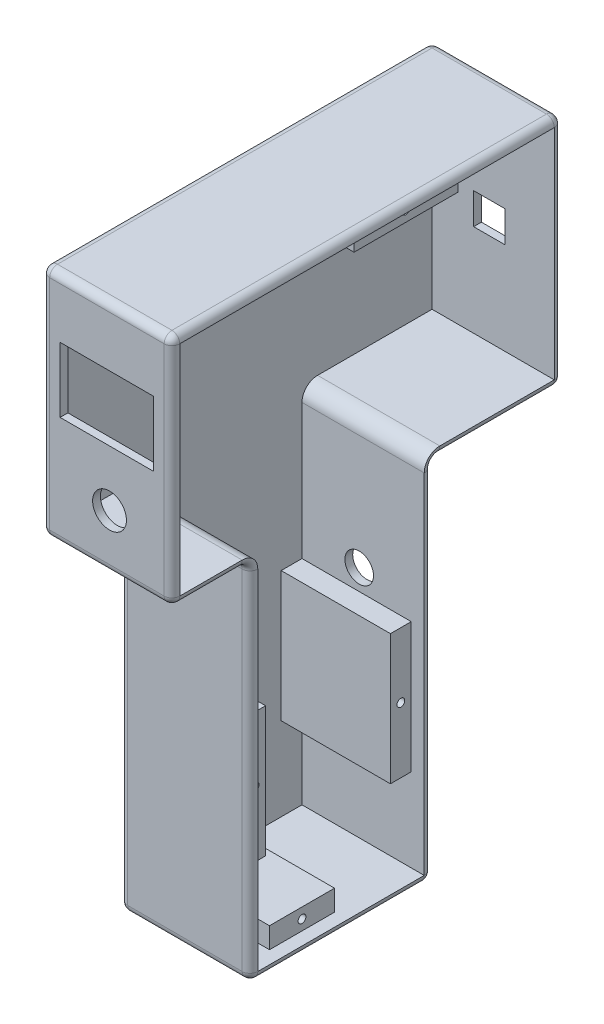
SolidWorks part; units mm, degrees
ref_plane "Front Plane" through (0, 0, 0) normal (0, 0, 1) x (1, 0, 0)
ref_plane "Top Plane" through (0, 0, 0) normal (0, 1, 0) x (1, 0, 0)
ref_plane "Right Plane" through (0, 0, 0) normal (1, 0, 0) x (0, 0, -1)
sketch "Esquisse1" plane through (0, 0, 0) normal (1, 0, 0) x (0, 0, -1)
  line L0 (0, 0) -> (70, 0)
  line L1 (70, 0) -> (70, 140)
  line L2 (70, 140) -> (120, 140)
  line L3 (120, 140) -> (120, 230)
  line L4 (120, 230) -> (-30, 230)
  line L5 (-30, 230) -> (-30, 140)
  line L6 (-30, 140) -> (0, 140)
  line L7 (0, 140) -> (0, 0)
  dimension "D1" = 70
  dimension "D2" = 140
  dimension "D3" = 50
  dimension "D4" = 30
  dimension "D5" = 90
  dimension "D6" = 90
extrude "Boss.-Extru.1" add sketch "Esquisse1" along normal blind 50
fillet "Congé1" radius 3 24 edges at (25, 140, -120) (25, 0, -70) (25, 140, -70) (0, 0, -35) (0, 70, -70) (0, 140, -95) (0, 185, -120) (0, 140, 15) (25, 140, 0) (25, 0, 0) (0, 70, 0) (50, 140, 15) (50, 185, -120) (50, 140, -95) (50, 70, -70) (50, 0, -35) (50, 70, 0) (50, 185, 30) (25, 140, 30) (0, 185, 30) (25, 230, -120) (50, 230, -45) (25, 230, 30) (0, 230, -45)
shell "Coque2" thickness 3 removed face at (50, 130.8485, -39)
sketch "Esquisse2" plane through (3, 0, 0) normal (1, 0, 0) x (0, 0, -1)
  line L0 (117, 227) -> (-27, 227) construction
  line L1 (45, 227) -> (85, 227)
  line L2 (45, 227) -> (45, 219)
  line L3 (45, 219) -> (85, 219)
  line L4 (85, 227) -> (85, 219)
  line L5 (3, 3) -> (3, 137) construction
  line L6 (3, 85) -> (11, 85)
  line L7 (3, 85) -> (3, 35)
  line L8 (3, 35) -> (11, 35)
  line L9 (11, 85) -> (11, 35)
  line L10 (67, 137) -> (67, 3) construction
  line L11 (67, 35) -> (59, 35)
  line L12 (67, 35) -> (67, 85)
  line L13 (67, 85) -> (59, 85)
  line L14 (59, 35) -> (59, 85)
  line L15 (67, 3) -> (3, 3) construction
  line L16 (12.5, 3) -> (37.5, 3)
  line L17 (12.5, 3) -> (12.5, 11)
  line L18 (12.5, 11) -> (37.5, 11)
  line L19 (37.5, 3) -> (37.5, 11)
  line L20 (117, 143) -> (117, 227) construction
  line L24 (3, 137) -> (3, 3) construction
  circle A0 centre (65, 223) radius 1.5
  circle A1 centre (7, 60) radius 1.5
  circle A2 centre (63, 60) radius 1.5
  circle A3 centre (25, 7) radius 1.5
  point P24 (65, 227)
  point P29 (63, 35)
  dimension "D14" = 3
  dimension "D15" = 4
  dimension "D18" = 3
  dimension "D19" = 3
  dimension "D20" = 3
  dimension "D22" = 4
  dimension "D23" = 4
  dimension "D1" = 40
  dimension "D2" = 8
  dimension "D3" = 8
  dimension "D4" = 50
  dimension "D5" = 50
  dimension "D6" = 8
  dimension "D7" = 8
  dimension "D8" = 25
  dimension "D9" = 32
  dimension "D10" = 32
  dimension "D11" = 32
  dimension "D12" = 9.5
  dimension "D13" = 12.5
  dimension "D16" = 25
  dimension "D17" = 25
  dimension "D21" = 20
  dimension "D24" = 4
extrude "Boss.-Extru.3" add sketch "Esquisse2" along normal blind 42
sketch "Esquisse3" plane through (0, 0, 30) normal (0, 0, 1) x (1, 0, 0)
  line L1 (7, 207.5) -> (43, 207.5)
  line L2 (7, 207.5) -> (7, 182.5)
  line L3 (7, 182.5) -> (43, 182.5)
  line L4 (43, 207.5) -> (43, 182.5)
  line L5 (47, 227) -> (3, 227) construction
  line L7 (3, 227) -> (3, 143) construction
  dimension "D1" = 25
  dimension "D2" = 36
  dimension "D3" = 19.5
  dimension "D4" = 4
extrude "Enlèv. mat.-Extru.1" cut sketch "Esquisse3" against normal blind 10
sketch "Esquisse5" plane through (0, 0, 30) normal (0, 0, 1) x (1, 0, 0)
  line L0 (47, 143) -> (47, 227) construction
  line L1 (3, 143) -> (47, 143) construction
  circle A0 centre (26, 161) radius 6.5
  dimension "D1" = 21
  dimension "D2" = 18
extrude "Enlèv. mat.-Extru.2" cut sketch "Esquisse5" against normal blind 10
sketch "Esquisse6" plane through (0, 0, -70) normal (0, 0, -1) x (-1, 0, 0)
  line L0 (-3, 3) -> (-3, 137) construction
  line L2 (-47, 3) -> (-3, 3) construction
  circle A0 centre (-25, 93) radius 5.5
  dimension "D1" = 11
  dimension "D2" = 22
  dimension "D3" = 90
extrude "Enlèv. mat.-Extru.3" cut sketch "Esquisse6" against normal blind 10
sketch "Esquisse7" plane through (0, 0, -120) normal (0, 0, -1) x (-1, 0, 0)
  line L0 (-3, 143) -> (-3, 227) construction
  line L1 (-31, 190.5) -> (-19, 190.5)
  line L2 (-31, 190.5) -> (-31, 178.5)
  line L3 (-31, 178.5) -> (-19, 178.5)
  line L4 (-19, 190.5) -> (-19, 178.5)
  line L6 (-47, 143) -> (-3, 143) construction
  dimension "D1" = 12
  dimension "D2" = 12
  dimension "D3" = 16
  dimension "D4" = 35.5
extrude "Enlèv. mat.-Extru.4" cut sketch "Esquisse7" against normal blind 10
